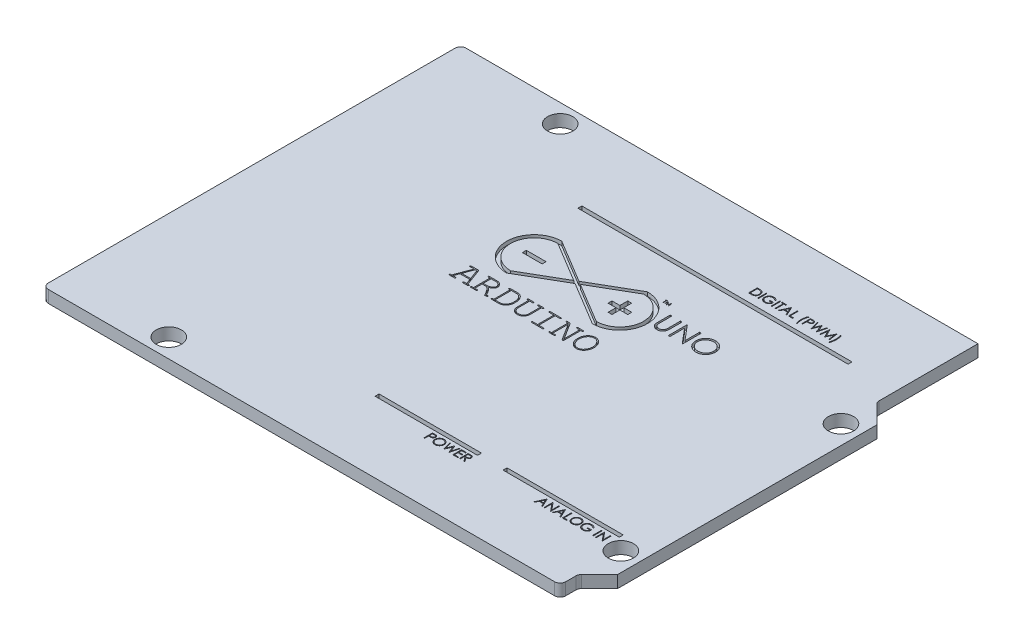
SolidWorks part; units mm, degrees
ref_plane "Plan de face" through (0, 0, 0) normal (0, 0, 1) x (1, 0, 0)
ref_plane "Plan de dessus" through (0, 0, 0) normal (0, 1, 0) x (1, 0, 0)
ref_plane "Plan de droite" through (0, 0, 0) normal (1, 0, 0) x (0, 0, -1)
sketch "Esquisse1" plane through (0, 0, 0) normal (0, 1, 0) x (1, 0, 0)
  line L0 (65.7, 53.05) -> (65.7, 40.2)
  line L1 (0, 0) -> (65.7, 0)
  line L2 (0, 0) -> (0, 53.05)
  line L3 (0, 53.05) -> (65.7, 53.05)
  line L4 (68.2, 4.8) -> (68.2, 37.7)
  line L5 (65.7, 40.2) -> (68.2, 37.7)
  line L6 (68.2, 4.8) -> (65.7, 2.3)
  line L7 (65.7, 2.3) -> (65.7, 0)
  circle A0 centre (15, 50.7) radius 1.6
  circle A1 centre (13.6, 2.4) radius 1.6
  circle A2 centre (65.8, 7.6) radius 1.6
  circle A3 centre (65.8, 35.55) radius 1.6
  dimension "D8" = 3.2
  dimension "D9" = 3.2
  dimension "D10" = 3.2
  dimension "D11" = 3.2
  dimension "D12" = 2.4
  dimension "D13" = 27.95
  dimension "D14" = 7.6
  dimension "D15" = 2.4
  dimension "D16" = 15
  dimension "D17" = 2.35
  dimension "D18" = 2.4
  dimension "D19" = 13.6
  dimension "D1" = 53.05
  dimension "D2" = 68.2
  dimension "D3" = 2.5
  dimension "D4" = 135
  dimension "D5" = 135
  dimension "D6" = 32.9
  dimension "D7" = 2.3
extrude "Boss.-Extru.1" add sketch "Esquisse1" along normal blind 1.55
fillet "Congé1" radius 0.7 5 edges at (65.7, 0.775, -40.2) (65.7, 0.775, -2.3) (65.7, 0.775, 0) (0, 0.775, -53.05) (0, 0.775, 0)
sketch "Sketch1" plane through (0, 1.55, 0) normal (0, 1, 0) x (1, 0, 0)
  line L0 (65.7, 53.05) -> (0.7, 53.05) construction
  line L1 (25.4017, 42.55) -> (59.7, 42.55)
  line L2 (25.4017, 43.05) -> (59.7, 43.05)
  line L3 (25.4017, 43.05) -> (25.4017, 42.55)
  line L4 (59.7, 43.05) -> (59.7, 42.55)
  line L5 (59.7, 42.55) -> (59.7448, 42.6405)
  line L6 (65.7, 40.4899) -> (65.7, 53.05) construction
  dimension "D1" = 0.5
  dimension "D2" = 10
  dimension "D3" = 6
extrude "Cut-Extrude1" cut sketch "Sketch1" against normal blind 0.5 contours L1 L3 L2 L4
sketch "Sketch2" plane through (0, 1.55, 0) normal (0, 1, 0) x (1, 0, 0)
  line L0 (57.7, 44.0663) -> (44.1775, 44.0663) construction
  line L1 (25.4017, 43.05) -> (59.7, 43.05) construction
  line L2 (65.7, 40.4899) -> (65.7, 53.05) construction
  text T0 "DIGITAL (PWM)" font "Century Gothic" height 1.1167
  dimension "D1" = 1.0163
  dimension "D2" = 8
extrude "Cut-Extrude2" cut sketch "Sketch2" against normal blind 0.5
sketch "Sketch3" plane through (0, 1.55, 0) normal (0, 1, 0) x (1, 0, 0)
  line L0 (0.7, 0) -> (65, 0) construction
  line L1 (33.2, 9.5) -> (46.2, 9.5)
  line L2 (33.2, 9.5) -> (33.2, 9)
  line L3 (33.2, 9) -> (46.2, 9)
  line L4 (46.2, 9.5) -> (46.2, 9)
  line L5 (49.45, 9.5) -> (64.2, 9.5)
  line L6 (49.45, 9.5) -> (49.45, 9)
  line L7 (49.45, 9) -> (64.2, 9)
  line L8 (64.2, 9.5) -> (64.2, 9)
  line L9 (63.7, 7.5) -> (53.3998, 7.5) construction
  line L10 (46.2, 7.5) -> (34.2198, 7.5) construction
  line L11 (68.2, 4.8) -> (68.2, 37.7) construction
  text T0 "POWER" font "Century Gothic" height 1.1167
  text T1 "ANALOG IN" font "Century Gothic" height 1.1167
  dimension "D1" = 9
  dimension "D2" = 9
  dimension "D3" = 0.5
  dimension "D4" = 0.5
  dimension "D5" = 13
  dimension "D6" = 14.75
  dimension "D7" = 1.5
  dimension "D8" = 22
  dimension "D9" = 22
  dimension "D10" = 4
  dimension "D11" = 4.5
extrude "Cut-Extrude3" cut sketch "Sketch3" against normal blind 0.5
sketch "Sketch5" plane through (0, 1.55, 0) normal (0, 1, 0) x (1, 0, 0)
  line L0 (28.004, 37.3981) -> (33.0823, 34.3397)
  line L1 (28.004, 30.8981) -> (33.5055, 34.0849)
  line L2 (39.007, 37.7716) -> (33.5055, 34.5849)
  line L3 (39.007, 31.2716) -> (33.9287, 34.33)
  line L4 (33.9287, 34.33) -> (39.007, 37.2716)
  line L5 (33.0823, 34.3397) -> (28.004, 31.3981)
  line L6 (33.5055, 34.5849) -> (28.004, 37.8981)
  line L7 (33.5055, 34.0849) -> (39.007, 30.7716)
  line L8 (39.257, 34.5216) -> (39.257, 35.5216)
  line L9 (26.754, 34.1481) -> (29.254, 34.1481)
  line L10 (26.754, 34.1481) -> (26.754, 34.6481)
  line L11 (26.754, 34.6481) -> (29.254, 34.6481)
  line L12 (29.254, 34.1481) -> (29.254, 34.6481)
  line L13 (26.754, 34.1481) -> (29.254, 34.6481) construction
  line L14 (26.754, 34.6481) -> (29.254, 34.1481) construction
  line L15 (37.757, 34.0216) -> (38.757, 34.0216)
  line L16 (37.757, 34.0216) -> (37.757, 34.5216)
  line L17 (37.757, 34.5216) -> (38.757, 34.5216)
  line L18 (40.257, 34.0216) -> (40.257, 34.5216)
  line L21 (38.757, 33.0216) -> (39.257, 33.0216)
  line L22 (39.257, 34.5216) -> (40.257, 34.5216)
  line L23 (38.757, 35.5216) -> (39.257, 35.5216)
  line L24 (39.257, 33.0216) -> (39.257, 34.0216)
  line L27 (38.757, 33.0216) -> (38.757, 34.0216)
  line L28 (38.757, 34.5216) -> (38.757, 35.5216)
  line L29 (39.257, 34.0216) -> (40.257, 34.0216)
  arc A2 (28.004, 37.3981) -> (28.004, 31.3981) centre (28.004, 34.3981) ccw
  arc A3 (39.007, 31.2716) -> (39.007, 37.2716) centre (39.007, 34.2716) ccw
  arc A4 (39.007, 30.7716) -> (39.007, 37.7716) centre (39.007, 34.2716) ccw
  arc A6 (28.004, 37.8981) -> (28.004, 30.8981) centre (28.004, 34.3981) ccw
  dimension "D1" = 0.5
  dimension "D2" = 2.5
  dimension "D3" = 6
  dimension "D4" = 6
  dimension "D5" = 0.5
  dimension "D6" = 0.5
  dimension "D7" = 2.5
  dimension "D8" = 2.5
extrude "Cut-Extrude4" cut sketch "Sketch5" against normal blind 0.5 contours L24 L29 L18 L22 L8 L23 L28 L17 L16 L15 L27 L21 | L6 A6 L1 L7 A4 L2 A2 L0 L5 A3 L3 L4 | L9 L12 L11 L10 region at (33.5055, 1.55, -34.3349) region at (39.007, 1.55, -34.2716) region at (28.004, 1.55, -34.3981)
sketch "Sketch6" plane through (0, 1.55, 0) normal (0, 1, 0) x (1, 0, 0)
  line L0 (24.504, 27.05) -> (42.507, 27.05) construction
  line L1 (42.7, 34.2716) -> (49.2, 34.2716) construction
  line L2 (40.5, 37.55) -> (42.5, 37.55) construction
  line L3 (65.7, 53.05) -> (0.7, 53.05) construction
  line L4 (68.2, 4.8) -> (68.2, 37.7) construction
  line L5 (0, 52.35) -> (0, 0.7) construction
  text T0 "ARDUINO" font "Courier New" height in points 11
  text T1 "UNO" font "Century Gothic" height in points 9
  text T2 "TM" font "Century Gothic" height 0.5
  dimension "D1" = 26
  dimension "D2" = 19
  dimension "D3" = 6.5
  dimension "D4" = 15.5
  dimension "D5" = 2
  dimension "D6" = 40.5
extrude "Cut-Extrude5" cut sketch "Sketch6" against normal blind 0.5
